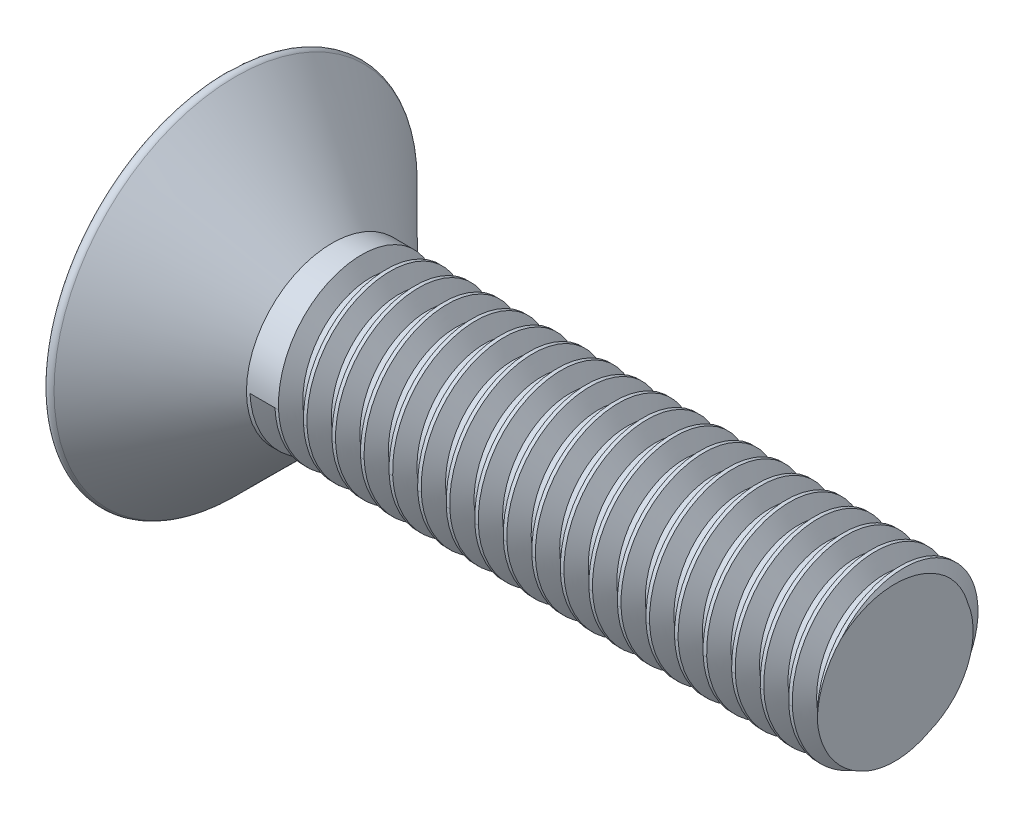
SolidWorks part; units mm, degrees
ref_plane "Front Plane" through (0, 0, 0) normal (0, 0, 1) x (1, 0, 0)
ref_plane "Top Plane" through (0, 0, 0) normal (0, 1, 0) x (1, 0, 0)
ref_plane "Right Plane" through (0, 0, 0) normal (1, 0, 0) x (0, 0, -1)
sketch "Sketch1" plane through (0, 0, 0) normal (0, 1, 0) x (1, 0, 0)
  line L0 (-8.5891, 0) -> (8.9417, 0) construction
  line L1 (-6.5237, 0) -> (-6.5237, 3.35)
  line L2 (-6.5237, 3.35) -> (-4.6637, 1.5)
  line L3 (-4.6637, 1.5) -> (5.3363, 1.5)
  line L4 (5.3363, 1.5) -> (5.3363, 0)
  line L5 (5.3363, 0) -> (-6.5237, 0)
  dimension "D1" = 6.7
  dimension "D2" = 3
  dimension "D3" = 10
  dimension "D4" = 1.86
revolve "Revolve1" add sketch "Sketch1" angle 360 about L0
fillet "Fillet1" radius 0.1 1 edges at (-6.5237, 0, 3.35)
thread "Thread1" pitch 0.5 method cut profile "Thread Profile2" start angle 0, offset 0.5, length 10, pitch 0.5, diameter 3
ref_plane "Plane2" through (5.8363, 0, 1.5) normal (0, -1, 0) x (0, 0, 1)
sketch "Thread Profile2" plane through (5.8363, 0, 1.5) normal (0, -1, 0) x (0, 0, 1)
  line L0 (0, 0) -> (0, 0.5) construction
  line L11 (0, 0) -> (0, 0.4375)
  line L12 (0, 0.4375) -> (-0.2706, 0.2812)
  line L13 (-0.2706, 0.2812) -> (-0.2706, 0.1562)
  line L15 (-0.2706, 0.1562) -> (0, 0)
  line L17 (-0.2706, 0.2187) -> (0, 0.2187) construction
  point P2 (0, 0)
  dimension "Pitch" = 0.5
  dimension "Profile_Angle" = 60
  dimension "Profile_Land" = 0.125
  dimension "Profile_Height" = 0.2706
sketch "Sketch6" plane through (-6.5237, 0, 0) normal (-1, 0, 0) x (0, 0, 1)
  line L1 (1.1547, 0) -> (0.5774, 1)
  line L2 (0.5774, 1) -> (-0.5774, 1)
  line L3 (-0.5774, 1) -> (-1.1547, 0)
  line L4 (-1.1547, 0) -> (-0.5774, -1)
  line L5 (-0.5774, -1) -> (0.5774, -1)
  line L6 (0.5774, -1) -> (1.1547, 0)
  circle A0 centre (0, 0) radius 1 construction
  dimension "D1" = 2
extrude "Cut-Extrude1" cut sketch "Sketch6" against normal blind 1.5
